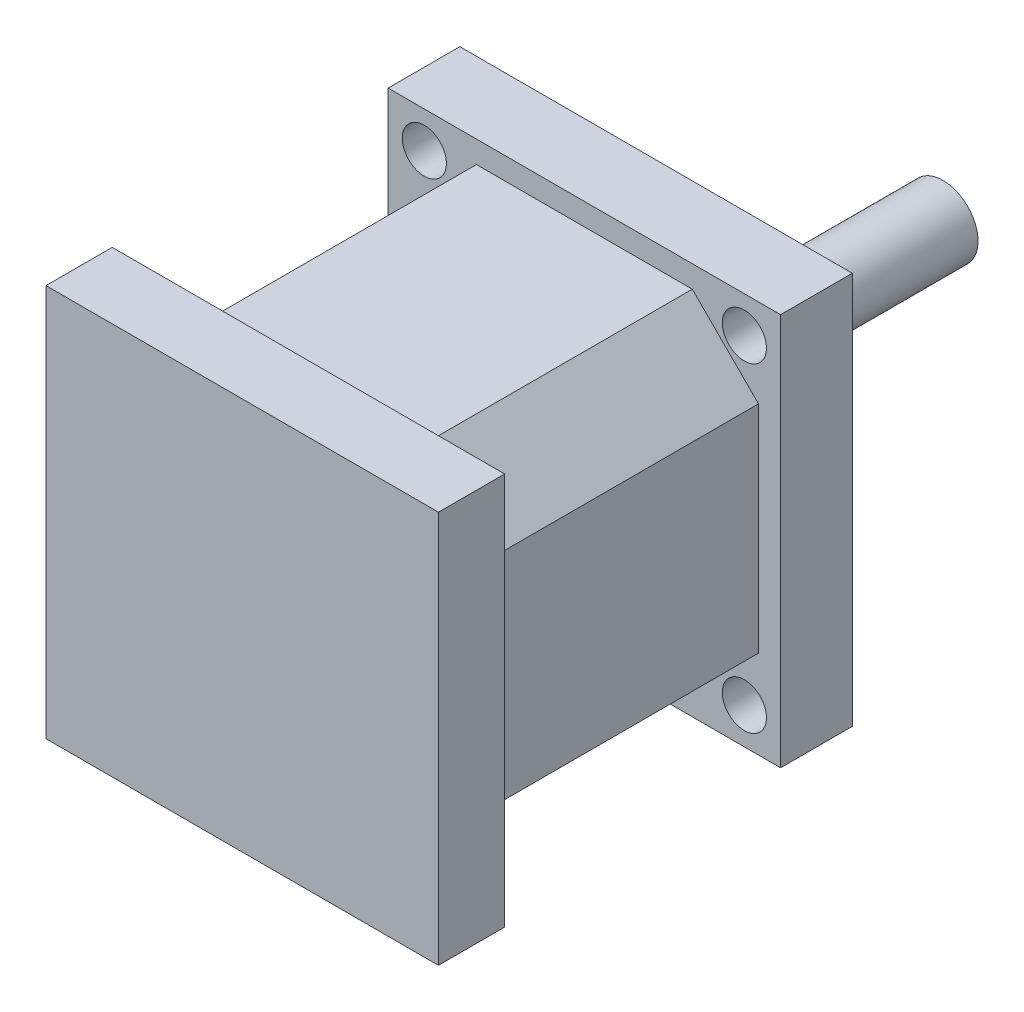
SolidWorks part; units mm, degrees
material "ABS"
ref_plane "Front Plane" through (0, 0, 0) normal (0, 0, 1) x (1, 0, 0)
ref_plane "Top Plane" through (0, 0, 0) normal (0, 1, 0) x (1, 0, 0)
ref_plane "Right Plane" through (0, 0, 0) normal (1, 0, 0) x (0, 0, -1)
sketch "Sketch1" plane through (0, 0, 0) normal (0, 0, 1) x (1, 0, 0)
  line L0 (21.15, 42.018) -> (21.15, -3.8447) construction
  line L1 (3.37, 2.8444) -> (38.93, 2.8444)
  line L2 (3.37, 2.8444) -> (3.37, 38.4044)
  line L3 (3.37, 38.4044) -> (38.93, 38.4044)
  line L4 (38.93, 2.8444) -> (38.93, 38.4044)
  line L5 (0, 20.6244) -> (51.3481, 20.6244) construction
  circle A4 centre (21.15, 20.6244) radius 11
  circle A5 centre (21.15, 20.6244) radius 2.5
  point P2 (3.37, 38.4044)
  point P4 (38.93, 3.1264)
  point P9 (38.4303, 3.1264)
  dimension "D5" = 22
  dimension "D6" = 5
  dimension "D1" = 17.78
extrude "Boss-Extrude1" add sketch "Sketch1" along normal blind 4.5 contours L2 L1 L4 L3 A4 | A4 A5 | A5 region at (3.8729, 20.6244, 0) region at (10.4611, 20.6244, 0) region at (21.15, 20.6244, 0)
sketch "Sketch2" plane through (0, 0, 4.5) normal (0, 0, 1) x (1, 0, 0)
  line L8 (3.37, 38.4044) -> (3.37, 2.8444)
  line L10 (3.37, 2.8444) -> (38.93, 2.8444)
  line L12 (38.93, 2.8444) -> (38.93, 38.4044)
  line L14 (38.93, 38.4044) -> (3.37, 38.4044)
  line L16 (3.37, 38.4044) -> (3.37, 2.8444)
  line L18 (3.37, 2.8444) -> (38.93, 2.8444)
  line L20 (38.93, 2.8444) -> (38.93, 38.4044)
  line L22 (38.93, 38.4044) -> (3.37, 38.4044)
  dimension "D1" = 0
extrude "Boss-Extrude2" add sketch "Sketch2" along normal blind 2
sketch "Sketch5" plane through (0, 0, 0) normal (0, 0, -1) x (-1, 0, 0)
  line L0 (-38.93, 20.6244) -> (-3.37, 20.6244) construction
  line L1 (-21.15, 2.8444) -> (-21.15, 38.4044) construction
  line L8 (-3.37, 2.8444) -> (-3.37, 38.4044)
  line L10 (-3.37, 38.4044) -> (-38.93, 38.4044)
  line L12 (-38.93, 38.4044) -> (-38.93, 2.8444)
  line L14 (-38.93, 2.8444) -> (-3.37, 2.8444)
  line L16 (-3.37, 2.8444) -> (-3.37, 38.4044)
  line L18 (-3.37, 38.4044) -> (-38.93, 38.4044)
  line L20 (-38.93, 38.4044) -> (-38.93, 2.8444)
  line L22 (-38.93, 2.8444) -> (-3.37, 2.8444)
  circle A0 centre (-21.15, 20.6244) radius 11
  dimension "D2" = 22
  dimension "D1" = 0
extrude "Boss-Extrude5" add sketch "Sketch5" along normal blind 2 contours A0
sketch "Sketch6" plane through (0, 0, -2) normal (0, 0, -1) x (-1, 0, 0)
  line L0 (-32.15, 20.6244) -> (-10.15, 20.6244) construction
  line L1 (-21.15, 31.6244) -> (-21.15, 9.6244) construction
  circle A0 centre (-21.15, 20.6244) radius 3.175
  circle A1 centre (-21.15, 20.6244) radius 11
  circle A2 centre (-21.15, 20.6244) radius 11
  dimension "D2" = 6.35
  dimension "D1" = 0
extrude "Boss-Extrude6" add sketch "Sketch6" along normal blind 24 contours A0
sketch "Sketch7" plane through (0, 0, 0) normal (0, 0, -1) x (-1, 0, 0)
  line L0 (-38.93, 20.6244) -> (-3.37, 20.6244) construction
  line L1 (-21.15, 2.8444) -> (-21.15, 38.4044) construction
  line L8 (-3.37, 2.8444) -> (-3.37, 38.4044)
  line L10 (-3.37, 38.4044) -> (-38.93, 38.4044)
  line L12 (-38.93, 38.4044) -> (-38.93, 2.8444)
  line L14 (-38.93, 2.8444) -> (-3.37, 2.8444)
  line L16 (-3.37, 2.8444) -> (-3.37, 38.4044)
  line L18 (-3.37, 38.4044) -> (-38.93, 38.4044)
  line L20 (-38.93, 38.4044) -> (-38.93, 2.8444)
  line L22 (-38.93, 2.8444) -> (-3.37, 2.8444)
  circle A0 centre (-35.65, 6.1244) radius 2
  circle A1 centre (-6.65, 6.1244) radius 2
  circle A2 centre (-6.65, 35.1244) radius 2
  circle A3 centre (-35.65, 35.1244) radius 2
  dimension "D2" = 4
  dimension "D3" = 29
  dimension "D4" = 29
  dimension "D1" = 0
extrude "Cut-Extrude3" cut sketch "Sketch7" against normal blind 29 contours A0 | A3 | A2 | A1
sketch "Sketch8" plane through (0, 0, 6.5) normal (0, 0, 1) x (1, 0, 0)
  line L4 (3.37, 2.8444) -> (38.93, 2.8444)
  line L5 (38.93, 2.8444) -> (38.93, 38.4044)
  line L6 (38.93, 38.4044) -> (3.37, 38.4044)
  line L7 (3.37, 38.4044) -> (3.37, 2.8444)
  line L8 (3.37, 2.8444) -> (38.93, 2.8444)
  line L9 (38.93, 2.8444) -> (38.93, 38.4044)
  line L10 (38.93, 38.4044) -> (3.37, 38.4044)
  line L11 (3.37, 38.4044) -> (3.37, 2.8444)
  line L20 (5.37, 4.8444) -> (36.93, 4.8444)
  line L21 (36.93, 4.8444) -> (36.93, 36.4044)
  line L22 (36.93, 36.4044) -> (5.37, 36.4044)
  line L23 (5.37, 36.4044) -> (5.37, 4.8444)
  line L24 (5.37, 4.8444) -> (36.93, 4.8444)
  line L25 (36.93, 4.8444) -> (36.93, 36.4044)
  line L26 (36.93, 36.4044) -> (5.37, 36.4044)
  line L27 (5.37, 36.4044) -> (5.37, 4.8444)
  dimension "D1" = 0
  dimension "D2" = 2
extrude "Boss-Extrude7" add sketch "Sketch8" along normal blind 25 contours L24 L25 L26 L27
sketch "Sketch9" plane through (0, 0, 31.5) normal (0, 0, 1) x (1, 0, 0)
  line L4 (3.37, 2.8444) -> (38.93, 2.8444)
  line L5 (38.93, 2.8444) -> (38.93, 38.4044)
  line L6 (38.93, 38.4044) -> (3.37, 38.4044)
  line L7 (3.37, 38.4044) -> (3.37, 2.8444)
  line L8 (3.37, 2.8444) -> (38.93, 2.8444)
  line L9 (38.93, 2.8444) -> (38.93, 38.4044)
  line L10 (38.93, 38.4044) -> (3.37, 38.4044)
  line L11 (3.37, 38.4044) -> (3.37, 2.8444)
  dimension "D1" = 0
extrude "Boss-Extrude8" add sketch "Sketch9" along normal blind 6
chamfer "Chamfer1" distance 6 angle 45 4 edges at (5.37, 4.8444, 19) (36.93, 4.8444, 19) (36.93, 36.4044, 19) (5.37, 36.4044, 19)
